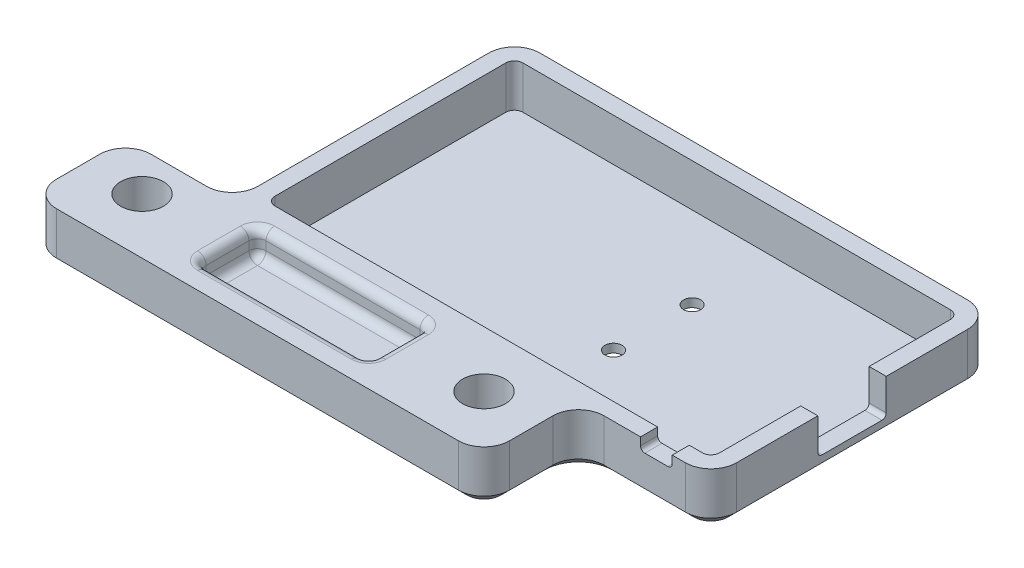
SolidWorks part; units mm, degrees
ref_plane "Front Plane" through (0, 0, 0) normal (0, 0, 1) x (1, 0, 0)
ref_plane "Top Plane" through (0, 0, 0) normal (0, 1, 0) x (1, 0, 0)
ref_plane "Right Plane" through (0, 0, 0) normal (1, 0, 0) x (0, 0, -1)
sketch "Sketch1" plane through (0, 0, 0) normal (0, 1, 0) x (1, 0, 0)
  line L0 (-28, 16.5) -> (28, 16.5)
  line L1 (-26, -14.5) -> (26, -14.5)
  line L2 (-26, -14.5) -> (-26, 14.5)
  line L3 (-26, 14.5) -> (26, 14.5)
  line L4 (26, -14.5) -> (26, 14.5)
  line L5 (-26, -14.5) -> (26, 14.5) construction
  line L6 (-26, 14.5) -> (26, -14.5) construction
  line L7 (28, -16.5) -> (28, 16.5)
  line L8 (-28, -16.5) -> (28, -16.5)
  line L9 (-28, -16.5) -> (-28, 16.5)
  point P0 (0, 0)
  dimension "D1" = 52
  dimension "D2" = 29
  dimension "D3" = 2
extrude "Boss-Extrude1" add sketch "Sketch1" along normal blind 5
sketch "Sketch2" plane through (0, 0, 0) normal (0, -1, 0) x (1, 0, 0)
  line L4 (-28, 16.5) -> (-28, -16.5)
  line L5 (-28, -16.5) -> (28, -16.5)
  line L6 (28, -16.5) -> (28, 16.5)
  line L7 (28, 16.5) -> (-28, 16.5)
  line L8 (-28, 16.5) -> (-28, -16.5)
  line L9 (-28, -16.5) -> (28, -16.5)
  line L10 (28, -16.5) -> (28, 16.5)
  line L11 (28, 16.5) -> (-28, 16.5)
  dimension "D1" = 0
extrude "Boss-Extrude2" add sketch "Sketch2" along normal blind 1
fillet "Fillet1" radius 3 4 edges at (28, 2, 16.5) (28, 2, -16.5) (-28, 2, -16.5) (-28, 2, 16.5)
fillet "Fillet2" radius 1 4 edges at (26, 2.5, 14.5) (-26, 2.5, 14.5) (-26, 2.5, -14.5) (26, 2.5, -14.5)
sketch "Sketch3" plane through (28, 0, 0) normal (1, 0, 0) x (0, 0, -1)
  line L0 (-13.5, 5) -> (13.5, 5) construction
  line L1 (-4, 9.2) -> (4, 9.2)
  line L2 (-4, 9.2) -> (-4, 0.8)
  line L3 (-4, 0.8) -> (4, 0.8)
  line L4 (4, 9.2) -> (4, 0.8)
  line L5 (-4, 9.2) -> (4, 0.8) construction
  line L6 (-4, 0.8) -> (4, 9.2) construction
  point P0 (0, 5)
  dimension "D1" = 8
  dimension "D2" = 4.2
extrude "Cut-Extrude1" cut sketch "Sketch3" against normal blind 10
sketch "Sketch4" plane through (28, 0, 0) normal (1, 0, 0) x (0, 0, -1)
  line L0 (-13.5, 5) -> (-4, 5) construction
  line L1 (-10.8805, 6.4) -> (-7.1805, 6.4)
  line L2 (-10.8805, 6.4) -> (-10.8805, 3.6)
  line L3 (-10.8805, 3.6) -> (-7.1805, 3.6)
  line L4 (-7.1805, 6.4) -> (-7.1805, 3.6)
  line L5 (-10.8805, 6.4) -> (-7.1805, 3.6) construction
  line L6 (-10.8805, 3.6) -> (-7.1805, 6.4) construction
  point P0 (-9.0305, 5)
  dimension "D1" = 3.7
  dimension "D2" = 1.4
extrude "Cut-Extrude2" [suppressed] cut sketch "Sketch4" against normal blind 10
sketch "Sketch9" plane through (0, 0, 16.5) normal (0, 0, 1) x (1, 0, 0)
  line L0 (-25, 5) -> (25, 5) construction
  line L1 (23.4617, 6.4) -> (19.7617, 6.4)
  line L2 (23.4617, 6.4) -> (23.4617, 3.6)
  line L3 (23.4617, 3.6) -> (19.7617, 3.6)
  line L4 (19.7617, 6.4) -> (19.7617, 3.6)
  line L5 (23.4617, 6.4) -> (19.7617, 3.6) construction
  line L6 (23.4617, 3.6) -> (19.7617, 6.4) construction
  point P0 (21.6117, 5)
  dimension "D1" = 1.4
  dimension "D2" = 3.7
extrude "Cut-Extrude4" cut sketch "Sketch9" against normal blind 3
fillet "Fillet3" [suppressed] radius 0.5
sketch "Sketch5" plane through (0, -1, 0) normal (0, -1, 0) x (1, 0, 0)
  line L0 (12.5, 16.5) -> (12.5, 27.55)
  line L1 (25, 16.5) -> (-25, 16.5) construction
  line L2 (12.5, 27.55) -> (-40.5, 27.55)
  line L3 (-40.5, 27.55) -> (-40.5, 16.5)
  line L4 (-40.5, 16.5) -> (-25, 16.5)
  line L5 (-28, 13.5) -> (-28, 16.5)
  line L6 (-28, 13.5) -> (-28, -13.5) construction
  line L7 (12.5, 16.5) -> (12.5, 15.4819)
  line L8 (12.5, 15.4819) -> (-28, 15.4819)
  arc A0 (-25, 16.5) -> (-28, 13.5) centre (-25, 13.5) ccw construction
  arc A1 (-25, 16.5) -> (-28, 13.5) centre (-25, 13.5) ccw
  circle A2 centre (6, 21.05) radius 4.5
  circle A3 centre (-34, 21.05) radius 4.5
  line M7 (25, 16.5) -> (-25, 16.5)
  arc M8 (-25, 16.5) -> (-28, 13.5) centre (-25, 13.5) ccw
  dimension "D1" = 9
  dimension "D2" = 6.5
  dimension "D3" = 40
  dimension "D4" = 6
  dimension "D5" = 6.5
  dimension "D6" = 6.5
  dimension "D7" = 4.55
ref_plane "Plane1" through (-25, 5, 16.5) normal (1, 0, 0) x (0, 0, -1)
extrude "Boss-Extrude6" add sketch "Sketch5" against normal blind 6 contours L3 L4 L0 L2 A3 A2 M7 | L8 L4 L5 M8 | L8 L5 M8 region at (-14, -1, 22.2956) region at (-27.1861, -1, 16.0943) region at (-27.7814, -1, 14.9996)
sketch "Sketch7" plane through (0, 5, 0) normal (0, 1, 0) x (1, 0, 0)
  circle A0 centre (6, -21.05) radius 4.5
  circle A1 centre (6, -21.05) radius 2.5
  circle A2 centre (-34, -21.05) radius 4.5
  circle A3 centre (-34, -21.05) radius 2.5
  dimension "D1" = 5
  dimension "D2" = 5
extrude "Boss-Extrude7" add sketch "Sketch7" against normal blind 5
fillet "Fillet4" radius 3 5 edges at (12.5, 2, 27.55) (12.5, 2, 16.5) (-40.5, 2, 27.55) (-40.5, 2, 16.5) (-28, 2, 16.5)
sketch "Sketch8" plane through (0, 5, 0) normal (0, 1, 0) x (1, 0, 0)
  line L0 (-34, -21.05) -> (6, -21.05) construction
  line L2 (-24, -17.55) -> (-4, -17.55)
  line L3 (-24, -17.55) -> (-24, -24.55)
  line L4 (-24, -24.55) -> (-4, -24.55)
  line L5 (-4, -17.55) -> (-4, -24.55)
  line L6 (-24, -17.55) -> (-4, -24.55) construction
  line L7 (-24, -24.55) -> (-4, -17.55) construction
  point P4 (-14, -21.05)
  dimension "D1" = 7
  dimension "D2" = 20
extrude "Cut-Extrude3" cut sketch "Sketch8" against normal blind 3
fillet "Fillet5" radius 1 12 edges at (-14, 2, 24.55) (-14, 5, 24.55) (-4, 3.5, 24.55) (-4, 2, 21.05) (-4, 5, 21.05) (-24, 2, 21.05) (-24, 3.5, 24.55) (-24, 5, 21.05) (-4, 3.5, 17.55) (-14, 2, 17.55) (-24, 3.5, 17.55) (-14, 5, 17.55)
chamfer "Chamfer2" distance 1 angle 45 16 edges at (0, -1, -16.5) (27.1213, -1, -15.6213) (-27.1213, -1, -15.6213) (28, -1, 0) (-28, -1, 0) (27.1213, -1, 15.6213) (-28.8787, -1, 15.6213) (20.25, -1, 16.5) (-34.25, -1, 16.5) (13.3787, -1, 17.3787) (-39.6213, -1, 17.3787) (12.5, -1, 22.025) (-40.5, -1, 22.025) (11.6213, -1, 26.6713) (-39.6213, -1, 26.6713) (-14, -1, 27.55)
fillet "Fillet6" radius 0.5 4 edges at (23.4617, 3.6, 15.5) (19.7617, 3.6, 15.5) (27, 0.8, 4) (27, 0.8, -4)
sketch "Sketch10" plane through (0, 0, 0) normal (0, 1, 0) x (1, 0, 0)
  line L0 (25, 14.5) -> (-25, 14.5) construction
  line L1 (26, -13.5) -> (26, 13.5) construction
  circle A0 centre (4.4, 4.9) radius 1
  circle A1 centre (4.4, -4.3) radius 1
  point P8 (4.4, -4.3)
  point P9 (0, 0)
  dimension "D1" = 2
  dimension "D2" = 2
  dimension "D3" = 9.2
  dimension "D4" = 9.6
  dimension "D5" = 21.6
extrude "Cut-Extrude5" cut sketch "Sketch10" against normal blind 3
